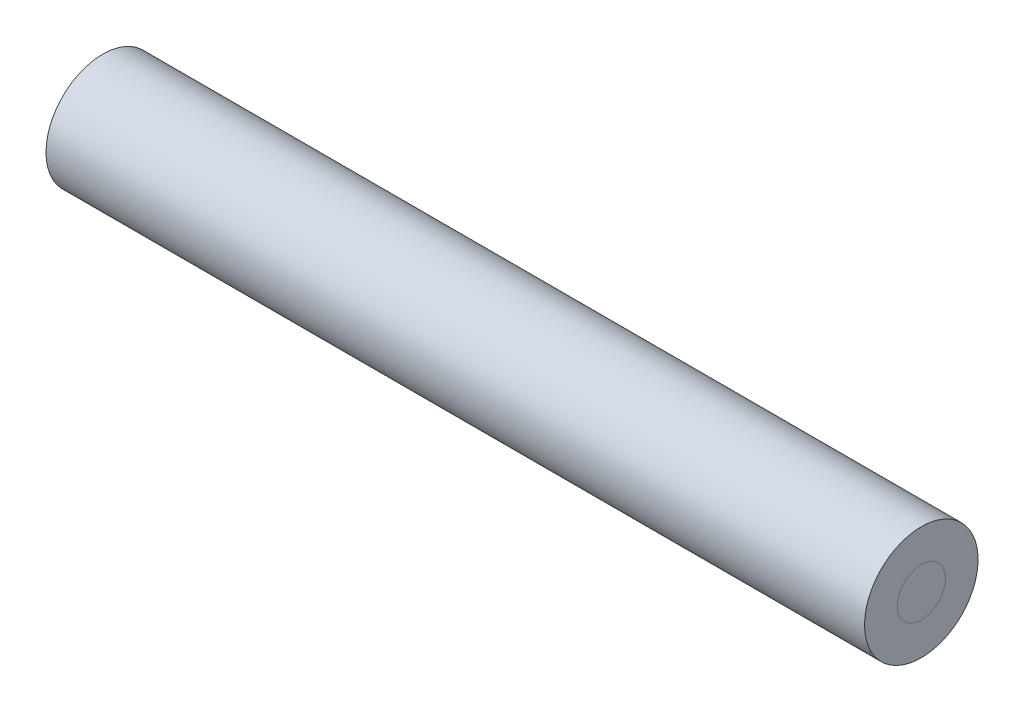
SolidWorks part; units mm, degrees
ref_plane "Front Plane" through (0, 0, 0) normal (0, 0, 1) x (1, 0, 0)
ref_plane "Top Plane" through (0, 0, 0) normal (0, 1, 0) x (1, 0, 0)
ref_plane "Right Plane" through (0, 0, 0) normal (1, 0, 0) x (0, 0, -1)
other "Configuration Table"
sketch "Sketch1" plane through (-3.3146, 0, 0) normal (-1, 0, 0) x (0, 0, 1)
  circle A0 centre (5.5588, 54.5748) radius 1.4097
  circle A1 centre (5.5588, 54.5748) radius 0.5969
  point P2 (5.5588, 54.5748)
  dimension "D1" = 2.8194
  dimension "D2" = 1.1938
extrude "Boss-Extrude1" add sketch "Sketch1" along normal blind 20.32 contours A1 region at (-3.3146, 54.5748, 5.5588)
extrude "Boss-Extrude2" add sketch "Sketch1<3>" along normal blind 20.32 separate body contours A0 A1 region at (-3.3146, 54.5748, 4.189)
sketch "Sketch1<3>" plane through (-3.3146, 0, 0) normal (-1, 0, 0) x (0, 0, 1) same geometry as "Sketch1"
